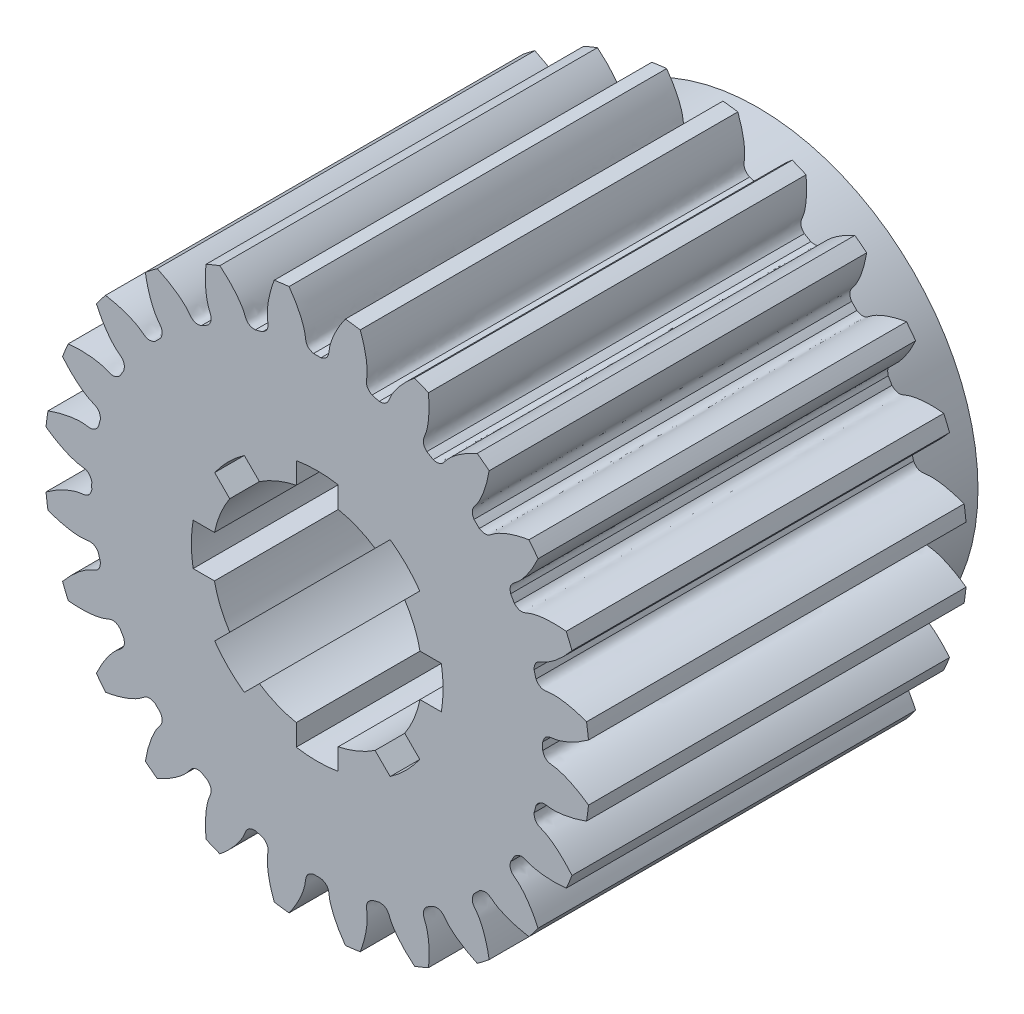
SolidWorks part; units mm, degrees
ref_plane "前视基准面" through (0, 0, 0) normal (0, 0, 1) x (1, 0, 0)
ref_plane "上视基准面" through (0, 0, 0) normal (0, 1, 0) x (1, 0, 0)
ref_plane "右视基准面" through (0, 0, 0) normal (1, 0, 0) x (0, 0, -1)
other "Configuration Table"
sketch "草图1" plane through (0, 0, 0) normal (0, 0, 1) x (1, 0, 0)
  circle A0 centre (0, 0) radius 13
  dimension "D1" = 26
extrude "凸台-拉伸1" add sketch "草图1" along normal blind 18
ref_axis "基准轴1" through (0, 0, 18) along (0, 0, -1)
sketch "草图2" plane through (0, 0, 0) normal (0, 0, 1) x (1, 0, 0)
  line L0 (0, 0) -> (0, 13) construction
  circle A0 centre (0, 0) radius 13 construction
  arc A1 (0.1768, 10.7485) -> (-0.1768, 10.7485) centre (0, 0) ccw
  arc A2 (3.1156, 14.6941) -> (-3.1156, 14.6941) centre (0, 0) ccw
  spline S0 degree 3 poles (0.1768, 10.7485) (0.5679, 10.8569) (0.539, 11.1157) (0.5863, 11.3727) (0.593, 11.4058) (0.6014, 11.4432) (0.6117, 11.4849) (0.6239, 11.5306) (0.6383, 11.5804) (0.655, 11.6343) (0.6742, 11.6921) (0.6961, 11.7537) (0.7208, 11.8191) (0.7484, 11.8882) (0.7793, 11.9609) (0.8133, 12.0371) (0.8509, 12.1166) (0.892, 12.1995) (0.9369, 12.2854) (0.9856, 12.3745) (1.0383, 12.4664) (1.0952, 12.5612) (1.1564, 12.6586) (1.222, 12.7585) (1.2921, 12.8608) (1.3669, 12.9654) (1.4464, 13.0721) (1.5309, 13.1807) (1.6203, 13.2911) (1.7148, 13.4032) (1.8145, 13.5167) (1.9196, 13.6315) (2.03, 13.7475) (2.1458, 13.8645) (2.2673, 13.9822) (2.3943, 14.1006) (2.5271, 14.2195) (2.6656, 14.3386) (2.8604, 14.4994) (3.0119, 14.6169) (3.1156, 14.6941) knots 0 0 0 0 0.143961 0.149818 0.156577 0.164236 0.172796 0.182258 0.19262 0.203884 0.216049 0.229115 0.243082 0.25795 0.273719 0.290389 0.30796 0.326433 0.345806 0.366081 0.387257 0.409333 0.432311 0.45619 0.48097 0.506651 0.533234 0.560717 0.589101 0.618387 0.648574 0.679661 0.71165 0.74454 0.778331 0.813023 0.848616 0.885111 0.922506 1 1 1 1
  spline S1 degree 3 poles (-0.1768, 10.7485) (-0.5679, 10.8569) (-0.539, 11.1157) (-0.5863, 11.3727) (-0.593, 11.4058) (-0.6014, 11.4432) (-0.6117, 11.4849) (-0.6239, 11.5306) (-0.6383, 11.5804) (-0.655, 11.6343) (-0.6742, 11.6921) (-0.6961, 11.7537) (-0.7208, 11.8191) (-0.7484, 11.8882) (-0.7793, 11.9609) (-0.8133, 12.0371) (-0.8509, 12.1166) (-0.892, 12.1995) (-0.9369, 12.2854) (-0.9856, 12.3745) (-1.0383, 12.4664) (-1.0952, 12.5612) (-1.1564, 12.6586) (-1.222, 12.7585) (-1.2921, 12.8608) (-1.3669, 12.9654) (-1.4464, 13.0721) (-1.5309, 13.1807) (-1.6203, 13.2911) (-1.7148, 13.4032) (-1.8145, 13.5167) (-1.9196, 13.6315) (-2.03, 13.7475) (-2.1458, 13.8645) (-2.2673, 13.9822) (-2.3943, 14.1006) (-2.5271, 14.2195) (-2.6656, 14.3386) (-2.8604, 14.4994) (-3.0119, 14.6169) (-3.1156, 14.6941) knots 0 0 0 0 0.143961 0.149818 0.156577 0.164236 0.172796 0.182258 0.19262 0.203884 0.216049 0.229115 0.243082 0.25795 0.273719 0.290389 0.30796 0.326433 0.345806 0.366081 0.387257 0.409333 0.432311 0.45619 0.48097 0.506651 0.533234 0.560717 0.589101 0.618387 0.648574 0.679661 0.71165 0.74454 0.778331 0.813023 0.848616 0.885111 0.922506 1 1 1 1
extrude "切除-拉伸1" cut sketch "草图2" along normal through all
pattern_circular "阵列(圆周)1" count 24 every 15 about axis through (0, 0, 18) along (0, 0, -1) of "切除-拉伸1"
sketch "草图3" plane through (0, 0, 0) normal (0, 0, 1) x (1, 0, 0)
  circle A0 centre (0, 0) radius 12 construction
  dimension "Dn" = 24
sketch "草图4" plane through (0, 0, 0) normal (0, 0, -1) x (-1, 0, 0)
  circle A0 centre (0, 0) radius 10.5
  dimension "D1" = 21
extrude "凸台-拉伸2" add sketch "草图4" along normal blind 3
sketch "草图5" plane through (0, 0, -3) normal (0, 0, -1) x (-1, 0, 0)
  line L0 (0, 13.1233) -> (0, -16.989) construction
  line L1 (-1, 4.899) -> (-1, 5.9161)
  line L2 (1, 4.899) -> (1, 5.9161)
  line L3 (2.757, 4.1712) -> (3.4762, 4.8904)
  line L4 (4.1712, 2.757) -> (4.8904, 3.4762)
  line L5 (4.899, 1) -> (5.9161, 1)
  line L6 (4.899, -1) -> (5.9161, -1)
  line L7 (4.1712, -2.757) -> (4.8904, -3.4762)
  line L8 (2.757, -4.1712) -> (3.4762, -4.8904)
  line L9 (1, -4.899) -> (1, -5.9161)
  line L10 (-1, -4.899) -> (-1, -5.9161)
  line L11 (-2.757, -4.1712) -> (-3.4762, -4.8904)
  line L12 (-4.1712, -2.757) -> (-4.8904, -3.4762)
  line L13 (-4.899, -1) -> (-5.9161, -1)
  line L14 (-4.899, 1) -> (-5.9161, 1)
  line L15 (-4.1712, 2.757) -> (-4.8904, 3.4762)
  line L16 (-2.757, 4.1712) -> (-3.4762, 4.8904)
  circle A0 centre (0, 0) radius 5
  circle A1 centre (0, 0) radius 6
  point P41 (0, 0)
  dimension "D1" = 12
  dimension "D2" = 10
  dimension "D3" = 2
  dimension "D4" = 8
extrude "切除-拉伸3" cut sketch "草图5" against normal through all both contours A0 L0 | L0 A0 | L0 A1 L1 A0 | A1 L0 A0 L2 | L16 A1 L15 A0 | L14 A1 L13 A0 | L12 A1 L11 A0 | A0 L0 A1 L9 | L0 A0 L10 A1 | L8 A1 L7 A0 | L6 A1 L5 A0 | L4 A1 L3 A0 region at (-0.5014, 5.4691, -3) region at (0.5014, 5.4691, -3) region at (-2.1221, 0, -3) region at (2.1221, 0, -3) region at (-0.5014, -5.4691, -3) region at (0.5014, -5.4691, -3) region at (-3.8673, 3.8673, -3) region at (3.8673, 3.8673, -3) region at (3.8673, -3.8673, -3) region at (-3.8673, -3.8673, -3) region at (-5.4691, 0, -3) region at (5.4691, 0, -3)
